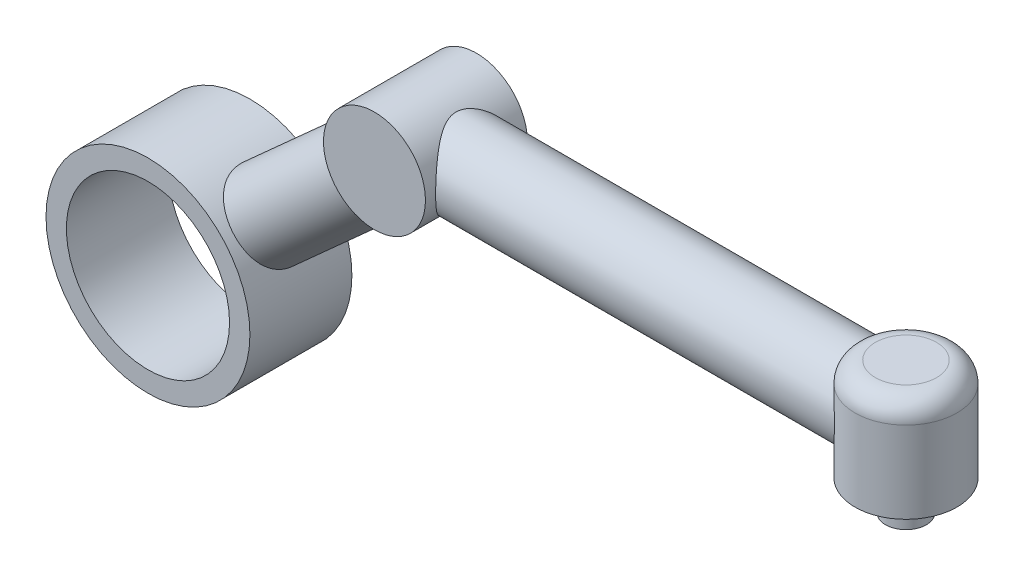
SolidWorks part; units mm, degrees
ref_plane "Front Plane" through (0, 0, 0) normal (0, 0, 1) x (1, 0, 0)
ref_plane "Top Plane" through (0, 0, 0) normal (0, 1, 0) x (1, 0, 0)
ref_plane "Right Plane" through (0, 0, 0) normal (1, 0, 0) x (0, 0, -1)
sketch "Sketch1" plane through (0, 0, 0) normal (0, 0, 1) x (1, 0, 0)
  line L0 (0, 0) -> (-261.777, -170) construction
  line L1 (0, 0) -> (202.5981, -170) construction
  line L2 (202.5981, -170) -> (202.5981, -64.2604) construction
  line L3 (-261.777, -170) -> (-261.777, -270) construction
  line L4 (202.5981, -170) -> (438.223, -170) construction
  line L5 (202.5981, -170) -> (91.5369, -270) construction
  line L6 (-286.777, -145) -> (-286.777, -195) construction
  line L7 (438.223, -170) -> (438.223, -270) construction
  line L8 (-236.777, -145) -> (-236.777, -195) construction
  line L9 (-286.777, -195) -> (-236.777, -195) construction
  line L10 (-236.777, -145) -> (-286.777, -145) construction
  line L11 (-261.777, -570) -> (438.223, -570) construction
  line L12 (-261.777, -670) -> (91.5369, -670) construction
  circle A0 centre (-261.777, -270) radius 50 construction
  circle A1 centre (-261.777, -270) radius 40 construction
  circle A2 centre (91.5369, -270) radius 40 construction
  circle A3 centre (91.5369, -270) radius 50 construction
  circle A4 centre (438.223, -270) radius 40 construction
  circle A5 centre (438.223, -270) radius 50 construction
  circle A6 centre (0, 0) radius 32.5 construction
  circle A7 centre (202.5981, -170) radius 25 construction
  point P13 (-286.777, -170)
  dimension "D7" = 80
  dimension "D8" = 100
  dimension "D13" = 65
  dimension "D14" = 50
  dimension "D1" = 50
  dimension "D2" = 107
  dimension "D3" = 170
  dimension "D4" = 100
  dimension "D5" = 48
  dimension "D6" = 700
  dimension "D9" = 25
  dimension "D10" = 50
  dimension "D11" = 400
  dimension "D12" = 100
sketch "Sketch3" plane through (0, 0, 0) normal (0, 0, 1) x (1, 0, 0)
  line L0 (-286.777, -195) -> (-261.777, -195) construction
  line L1 (-286.777, -195) -> (-236.777, -195) construction
  line L2 (-286.777, -195) -> (-286.777, -145) construction
  line L3 (-261.777, -195) -> (-261.777, -145) construction
  line L4 (-236.777, -145) -> (-286.777, -145) construction
  line L5 (438.223, -195) -> (438.223, -145) construction
  line L6 (438.223, -170) -> (438.223, -270) construction
  line L7 (438.223, -195) -> (413.223, -195)
  line L8 (413.223, -195) -> (413.223, -155)
  line L9 (423.223, -145) -> (438.223, -145)
  line L10 (438.223, -195) -> (438.223, -145)
  arc A0 (413.223, -155) -> (423.223, -145) centre (423.223, -155) cw
  dimension "D1" = 10
revolve "Revolve2" add sketch "Sketch3" angle 360 about L10
sketch "Sketch4" plane through (0, 0, 0) normal (0, 0, 1) x (1, 0, 0)
  line L0 (438.223, -170) -> (397.1595, -170)
  line L1 (202.5981, -170) -> (438.223, -170) construction
sweep "Cut-Sweep1" cut path "Sketch4" circular profile diameter 40 parameters "D3"=40
sketch "Sketch27" plane through (0, 0, 0) normal (0, 0, 1) x (1, 0, 0)
  circle A0 centre (202.5981, -170) radius 25
  circle A1 centre (202.5981, -170) radius 25 construction
  circle A2 centre (91.5369, -270) radius 40
  circle A3 centre (91.5369, -270) radius 50
  circle A4 centre (91.5369, -270) radius 40 construction
  circle A5 centre (91.5369, -270) radius 50 construction
extrude "Boss-Extrude1" add sketch "Sketch27" along normal mid plane 50 separate body
sketch "Sketch28" plane through (0, 0, 0) normal (0, 0, 1) x (1, 0, 0)
  line L0 (294.7517, -170) -> (346.1628, -170)
  line L1 (202.5981, -170) -> (438.223, -170) construction
sweep "Sweep1" add path "Sketch28" circular profile diameter 40 parameters "D3"=40
sweep "Cut-Sweep2" cut path "Sketch28<2>" circular profile diameter 30 parameters "D3"=30
sketch "Sketch28<2>" plane through (0, 0, 0) normal (0, 0, 1) x (1, 0, 0) same geometry as "Sketch28"
sketch "Sketch53" plane through (294.7517, 0, 0) normal (-1, 0, 0) x (0, 0, 1)
  circle A0 centre (0, -170) radius 15 construction
  circle A1 centre (0, -170) radius 20
  circle A2 centre (0, -170) radius 20
  circle A3 centre (0, -170) radius 15
  dimension "D1" = 0
extrude "Boss-Extrude2" add sketch "Sketch53" along normal up to next
sketch "Sketch54" plane through (346.1628, 0, 0) normal (1, 0, 0) x (0, 0, -1)
  circle A0 centre (0, -170) radius 15 construction
  circle A1 centre (0, -170) radius 20
  circle A2 centre (0, -170) radius 20
  circle A3 centre (0, -170) radius 15
  dimension "D1" = 0
extrude "Boss-Extrude3" add sketch "Sketch54" along normal up to next
sketch "Sketch55" plane through (0, 0, 0) normal (0, 0, 1) x (1, 0, 0)
  line L0 (147.0675, -220) -> (168.3495, -200.8376)
  line L1 (202.5981, -170) -> (91.5369, -270) construction
sweep "Sweep2" add path "Sketch55" circular profile diameter 40 parameters "D3"=40
sweep "Cut-Sweep3" cut path "Sketch55<2>" circular profile diameter 30 parameters "D3"=30
sketch "Sketch55<2>" plane through (0, 0, 0) normal (0, 0, 1) x (1, 0, 0) same geometry as "Sketch55"
sketch "Sketch84" plane through (-28.1773, -25.371, 0) normal (-0.7431, -0.6691, 0) x (0, 0, 1)
  circle A0 centre (0, -261.8992) radius 15 construction
  circle A1 centre (0, -261.8992) radius 20
  circle A2 centre (0, -261.8992) radius 20
  circle A3 centre (0, -261.8992) radius 15
  dimension "D1" = 0
extrude "Boss-Extrude4" add sketch "Sketch84" along normal up to next
sketch "Sketch85" plane through (-6.8953, -6.2085, 0) normal (0.7431, 0.6691, 0) x (0, 0, -1)
  circle A0 centre (0, -261.8992) radius 15 construction
  circle A1 centre (0, -261.8992) radius 20
  circle A2 centre (0, -261.8992) radius 20
  circle A3 centre (0, -261.8992) radius 15
  dimension "D1" = 0
extrude "Boss-Extrude5" add sketch "Sketch85" along normal up to next
sketch "Sketch86" plane through (0, -195, 0) normal (0, -1, 0) x (1, 0, 0)
  line L0 (488.223, 0) -> (388.223, 0) construction
  circle A0 centre (438.223, 0) radius 10
  dimension "D1" = 20
extrude "Boss-Extrude6" add sketch "Sketch86" along normal blind 15
